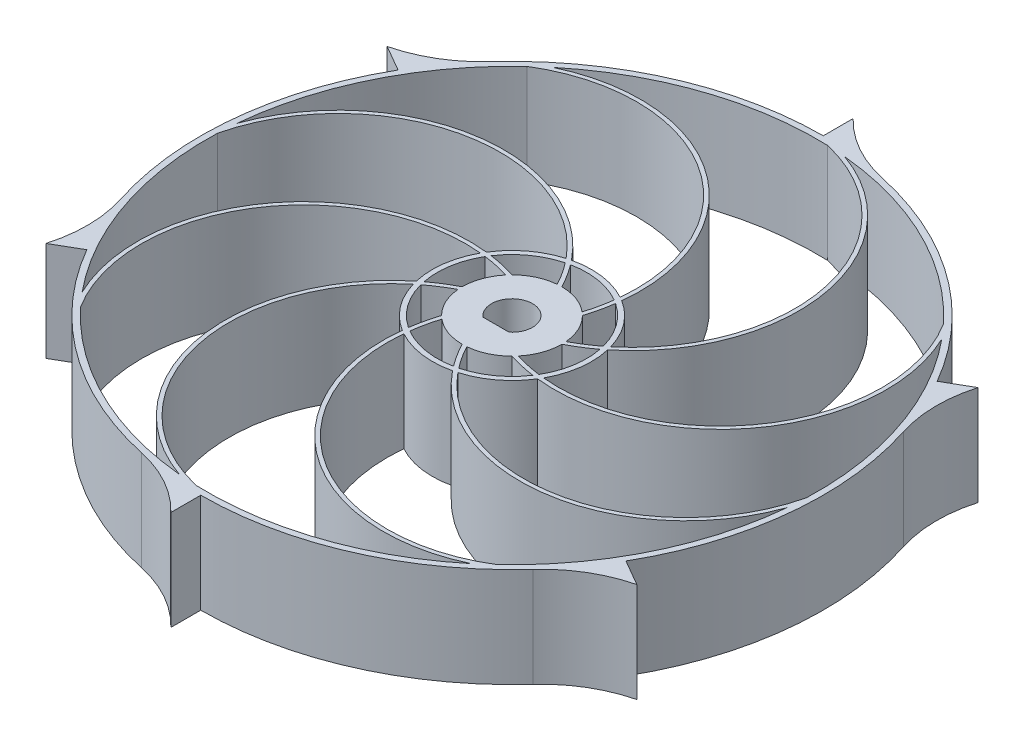
SolidWorks part; units mm, degrees
ref_plane "Front Plane" through (0, 0, 0) normal (0, 0, 1) x (1, 0, 0)
ref_plane "Top Plane" through (0, 0, 0) normal (0, 1, 0) x (1, 0, 0)
ref_plane "Right Plane" through (0, 0, 0) normal (1, 0, 0) x (0, 0, -1)
sketch "Sketch1" plane through (0, 0, 0) normal (0, 1, 0) x (1, 0, 0)
  line L0 (-2.603, -3.2) -> (2.603, -3.2)
  arc A0 (2.603, -3.2) -> (-2.603, -3.2) centre (0, 0) ccw
  circle A1 centre (0, 0) radius 62.5
  circle A28 centre (0, 0) radius 10
  circle A29 centre (0, 0) radius 61.3
  point P78 (0, 0)
  dimension "D1" = 8.25
  dimension "D2" = 125
  dimension "D3" = 20
  dimension "D7" = 3.2
  dimension "D4" = 1.2
extrude "Boss-Extrude1" add sketch "Sketch1" along normal blind 20 contours A1 A29 | A28 A0 L0 region at (-62.3232, 0, 0) region at (-9.7172, 0, 0)
sketch "Sketch4" plane through (0, 0, 0) normal (0, 1, 0) x (1, 0, 0)
  line L0 (-9.6325, -0.7106) -> (-10, 0)
  line L1 (0.1275, -61.7102) -> (0, -62.5)
  arc A0 (0, -62.5) -> (-10, 0) centre (5.3098, -29.6004) cw
  circle A1 centre (0, 0) radius 62.5 construction
  circle A2 centre (0, 0) radius 10 construction
  arc A3 (0.1275, -61.7102) -> (-9.6325, -0.7106) centre (5.3098, -29.6004) cw
  dimension "D1" = 0.8
extrude "Boss-Extrude4" add sketch "Sketch4" along normal up to surface (20 mm away) up to face at (0, 20, 61.3)
ref_axis "Axis1" through (0, 21, 0) along (0, -1, 0)
pattern_circular "CirPattern1" count 8 over 360 about axis through (0, 21, 0) along (0, -1, 0) of "Boss-Extrude4"
sketch "Sketch2" plane through (0, 0, 0) normal (0, 1, 0) x (1, 0, 0)
  circle A0 centre (0, 0) radius 15
  circle A1 centre (0, 0) radius 16
  dimension "D1" = 30
  dimension "D2" = 1
extrude "Boss-Extrude2" add sketch "Sketch2" along normal up to surface (20 mm away) up to face at (22.0804, 20, 26.8353)
sketch "Sketch3" plane through (0, 0, 0) normal (0, 1, 0) x (1, 0, 0)
  line L0 (0, -62.5) -> (0, -68.5)
  line L6 (-54.1266, -31.25) -> (-59.3227, -34.25)
  line L7 (-54.1266, 31.25) -> (-59.3227, 34.25)
  line L8 (0, 62.5) -> (0, 68.5)
  line L9 (54.1266, 31.25) -> (59.3227, 34.25)
  line L10 (54.1266, -31.25) -> (59.3227, -34.25)
  arc A1 (0, -68.5) -> (-13.2805, -61.0727) centre (-18.8262, -86.5757) ccw
  circle A17 centre (0, 0) radius 62.5 construction
  circle A18 centre (0, 0) radius 62.5
  arc A19 (-59.3227, -34.25) -> (-59.5308, -19.0351) centre (-84.3899, -26.9839) ccw
  arc A20 (-59.3227, 34.25) -> (-46.2503, 42.0376) centre (-65.5637, 59.5918) ccw
  arc A21 (0, 68.5) -> (13.2805, 61.0727) centre (18.8262, 86.5757) ccw
  arc A22 (59.3227, 34.25) -> (59.5308, 19.0351) centre (84.3899, 26.9839) ccw
  arc A23 (59.3227, -34.25) -> (46.2503, -42.0376) centre (65.5637, -59.5918) ccw
  point P9 (0, 0)
  point P11 (0, 0)
  point P30 (0, 0)
  point P33 (0, 0)
  dimension "D1" = 6
  dimension "D2" = 6
extrude "Boss-Extrude3" add sketch "Sketch3" along normal up to surface (20 mm away) contours A19 L6 A18 | A18 A1 L0 | A23 L10 A18 | A22 L9 A18 | A21 L8 A18 | A20 L7 A18 region at (-3.2274, 0, 64.1222) region at (53.9177, 0, 34.8561) region at (-57.1451, 0, 29.2661) region at (-53.9177, 0, -34.8561) region at (57.1451, 0, -29.2661) region at (3.2274, 0, -64.1222) up to face at (-10.3412, 20, 6.239)
